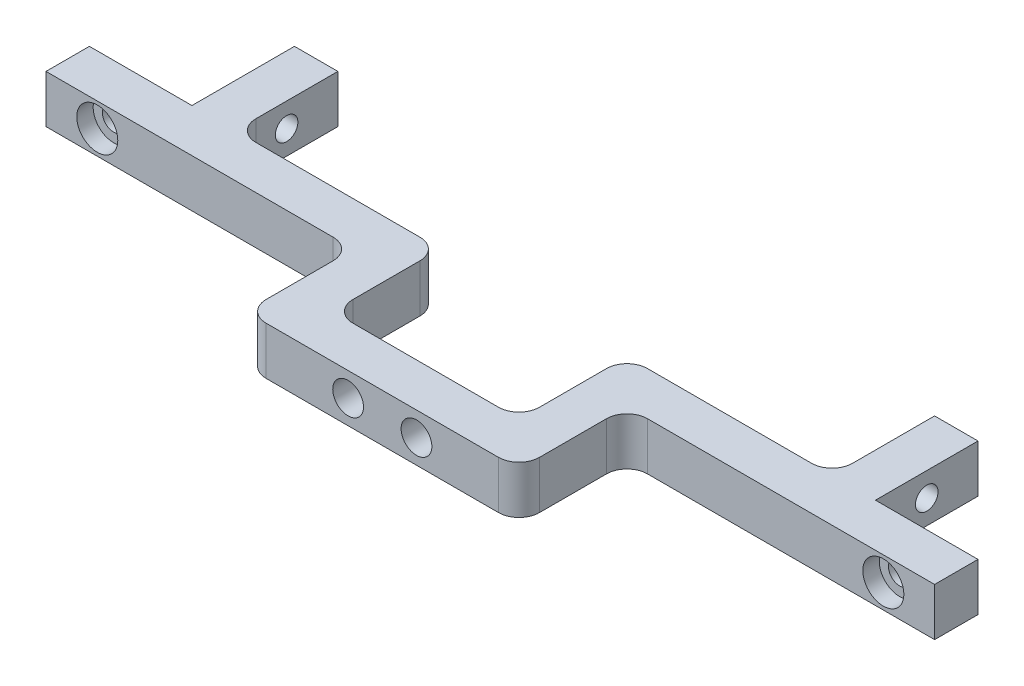
SolidWorks part; units mm, degrees
ref_plane "Front Plane" through (0, 0, 0) normal (0, 0, 1) x (1, 0, 0)
ref_plane "Top Plane" through (0, 0, 0) normal (0, 1, 0) x (1, 0, 0)
ref_plane "Right Plane" through (0, 0, 0) normal (1, 0, 0) x (0, 0, -1)
sketch "Sketch1" plane through (0, 0, 0) normal (0, 1, 0) x (1, 0, 0)
  line L1 (43.65, 15.8) -> (43.65, 30.8)
  line L2 (43.65, 30.8) -> (50, 30.8)
  line L3 (50, 30.8) -> (50, 15.8)
  line L6 (-50, 30.8) -> (-43.65, 30.8)
  line L7 (-43.65, 30.8) -> (-43.65, 15.8)
  line L9 (0, 52.9472) -> (0, -21.9318) construction
  line L10 (50, 15.8) -> (65, 15.8)
  line L13 (65, 15.8) -> (65, 9.45)
  line L15 (-65, 15.8) -> (-65, 9.45)
  line L17 (-50, 15.8) -> (-65, 15.8)
  line L18 (-50, 30.8) -> (-50, 15.8)
  line L20 (-43.65, 15.8) -> (-13.65, 15.8)
  line L22 (-13.65, 15.8) -> (-13.65, 0)
  line L23 (-13.65, 0) -> (13.65, 0)
  line L24 (13.65, 0) -> (13.65, 15.8)
  line L25 (13.65, 15.8) -> (43.65, 15.8)
  line L26 (65, 9.45) -> (20, 9.45)
  line L27 (20, 9.45) -> (20, -6.35)
  line L28 (20, -6.35) -> (-20, -6.35)
  line L29 (-20, -6.35) -> (-20, 9.45)
  line L30 (-20, 9.45) -> (-65, 9.45)
  dimension "D4" = 6.35
  dimension "D5" = 15
  dimension "D6" = 6.35
  dimension "D1" = 30
  dimension "D8" = 30
  dimension "D9" = 27.3
  dimension "D3" = 15
  dimension "D7" = 6.35
  dimension "D10" = 6.35
  dimension "D2" = 15
extrude "Boss-Extrude1" add sketch "Sketch1" along normal blind 7
sketch "Sketch2" plane through (50, 0, 0) normal (1, 0, 0) x (0, 0, -1)
  line L0 (30.8, 7) -> (30.8, 0) construction
  circle A0 centre (23.3, 3.5) radius 1.65
  dimension "D1" = 3.3
  dimension "D2" = 7.5
extrude "Cut-Extrude1" cut sketch "Sketch2" against normal through all
sketch "Sketch3" plane through (0, 0, -15.8) normal (0, 0, -1) x (-1, 0, 0)
  line L0 (-65, 3.5) -> (65, 3.5) construction
  line L3 (-65, 7) -> (-65, 0) construction
  line L4 (65, 7) -> (65, 0) construction
  circle A0 centre (-57.5, 3.5) radius 1.65
  circle A1 centre (57.5, 3.5) radius 1.65
  point P2 (0, 0)
  point P3 (0, 0)
  dimension "D2" = 3.3
  dimension "D4" = 3.3
  dimension "D1" = 7.5
  dimension "D3" = 7.5
fillet "Fillet1" radius 3 10 edges at (-43.65, 3.5, -15.8) (43.65, 3.5, -15.8) (20, 3.5, 6.35) (20, 3.5, -9.45) (-20, 3.5, -9.45) (-20, 3.5, 6.35) (13.65, 3.5, 0) (13.65, 3.5, -15.8) (-13.65, 3.5, -15.8) (-13.65, 3.5, 0)
extrude "Cut-Extrude4" cut sketch "Sketch3" against normal up to surface (6.35 mm away) up to face at (44, 3.5, -9.45)
sketch "Sketch5" plane through (0, 0, 6.35) normal (0, 0, 1) x (1, 0, 0)
  line L0 (-65, 3.5) -> (65, 3.5) construction
  line L1 (-65, 7) -> (-65, 0) construction
  line L2 (65, 7) -> (65, 0) construction
  line L3 (0, 7) -> (0, 0) construction
  line L4 (-17, 7) -> (17, 7) construction
  circle A0 centre (5, 3.5) radius 2.25
  circle A1 centre (-5, 3.5) radius 2.25
  point P13 (0, 0)
  dimension "D1" = 4.5
  dimension "D2" = 5
extrude "Cut-Extrude5" cut sketch "Sketch5" against normal up to surface (6.35 mm away) up to face at (0, 3.5, 0)
sketch "Sketch6" plane through (0, 0, -9.45) normal (0, 0, 1) x (1, 0, 0)
  circle A0 centre (-57.5, 3.5) radius 3
  circle A1 centre (57.5, 3.5) radius 3
  dimension "D1" = 6
extrude "Cut-Extrude6" cut sketch "Sketch6" against normal blind 2.4
equation "\"D6@Sketch1\"=\"D4@Sketch1\""
